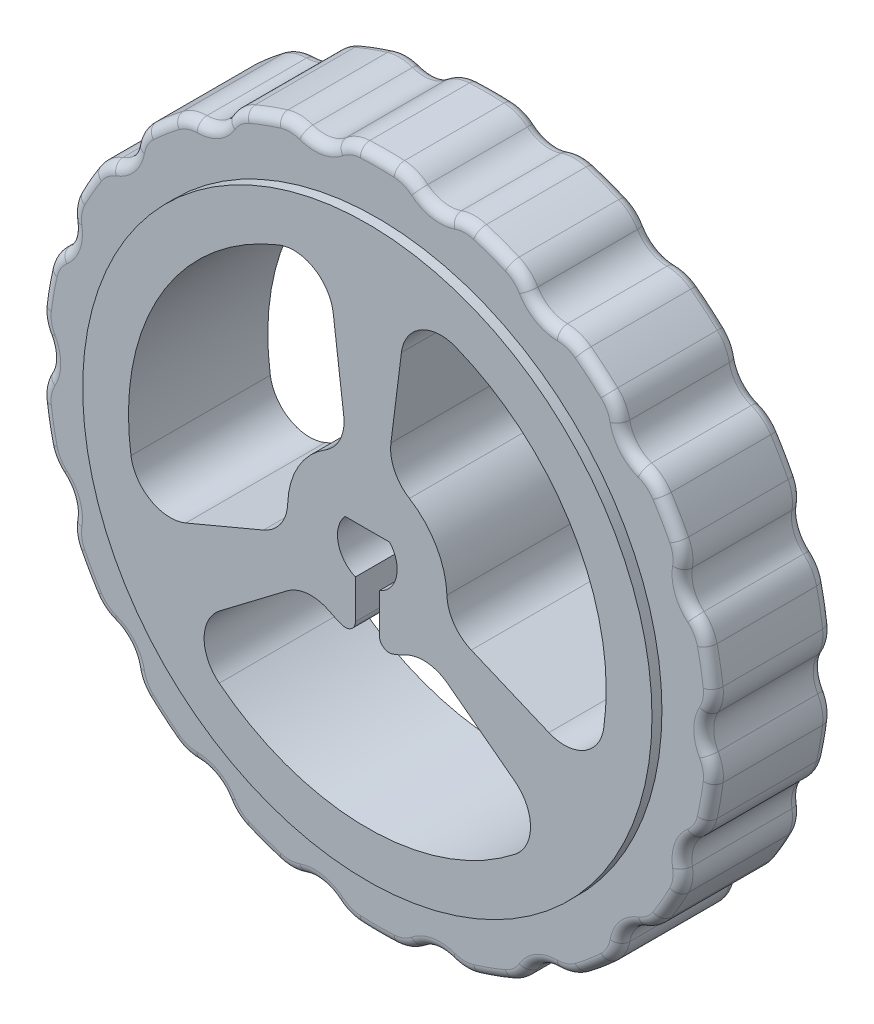
SolidWorks part; units mm, degrees
material "ABS"
ref_plane "前视基准面" through (0, 0, 0) normal (0, 0, 1) x (1, 0, 0)
ref_plane "上视基准面" through (0, 0, 0) normal (0, 1, 0) x (1, 0, 0)
ref_plane "右视基准面" through (0, 0, 0) normal (1, 0, 0) x (0, 0, -1)
sketch "草图1" plane through (0, 0, 0) normal (0, 0, 1) x (1, 0, 0)
  line L0 (0, 0) -> (0, 20.2054) construction
  line L1 (-2, 11.8322) -> (-1, 3.873)
  line L2 (2, 11.8322) -> (1, 3.873)
  line L3 (11.247, -4.184) -> (3.8541, -1.0705)
  line L4 (9.247, -7.6481) -> (2.8541, -2.8025)
  line L5 (-9.247, -7.6481) -> (-2.8541, -2.8025)
  line L6 (-11.247, -4.184) -> (-3.8541, -1.0705)
  line L7 (1.118, 1) -> (-1.118, 1)
  line L8 (0.6, -3.9547) -> (0.6, -1.3748)
  line L9 (-0.6, -3.9547) -> (-0.6, -1.3748)
  circle A0 centre (0, 0) radius 17
  arc A1 (-2, 11.8322) -> (-11.247, -4.184) centre (0, 0) ccw
  arc A2 (-1.118, 1) -> (-0.6, -1.3748) centre (0, 0) ccw
  arc A3 (-1, 3.873) -> (-3.8541, -1.0705) centre (0, 0) ccw
  arc A4 (-9.247, -7.6481) -> (9.247, -7.6481) centre (0, 0) ccw
  arc A5 (-2.8541, -2.8025) -> (-0.6, -3.9547) centre (0, 0) ccw
  arc A6 (3.8541, -1.0705) -> (1, 3.873) centre (0, 0) ccw
  arc A7 (11.247, -4.184) -> (2, 11.8322) centre (0, 0) ccw
  arc A8 (0.6, -1.3748) -> (1.118, 1) centre (0, 0) ccw
  arc A9 (0.6, -3.9547) -> (2.8541, -2.8025) centre (0, 0) ccw
  point P19 (0, 0)
  dimension "D1" = 34
  dimension "D2" = 3
  dimension "D3" = 4
  dimension "D4" = 12
  dimension "D5" = 1
  dimension "D6" = 2
  dimension "D8" = 1
  dimension "D9" = 1.2
  dimension "D7" = 3
extrude "凸台-拉伸1" add sketch "草图1" along normal mid plane 6
sketch "草图3" plane through (0, 0, 0) normal (0, 0, 1) x (1, 0, 0)
  line L2 (2, 11.8322) -> (1, 3.873)
  line L3 (3.8541, -1.0705) -> (11.247, -4.184)
  line L4 (2, 11.8322) -> (1, 3.873)
  line L5 (3.8541, -1.0705) -> (11.247, -4.184)
  line L6 (-1, 3.873) -> (-2, 11.8322)
  line L7 (-11.247, -4.184) -> (-3.8541, -1.0705)
  line L8 (-1, 3.873) -> (-2, 11.8322)
  line L9 (-11.247, -4.184) -> (-3.8541, -1.0705)
  line L10 (-2.8541, -2.8025) -> (-9.247, -7.6481)
  line L11 (9.247, -7.6481) -> (2.8541, -2.8025)
  line L12 (-2.8541, -2.8025) -> (-9.247, -7.6481)
  line L13 (9.247, -7.6481) -> (2.8541, -2.8025)
  line L17 (1.118, 1) -> (-1.118, 1)
  line L18 (1.118, 1) -> (-1.118, 1)
  line L19 (0.6, -3.9547) -> (0.6, -1.3748)
  line L20 (0.6, -3.9547) -> (0.6, -1.3748)
  line L21 (9.247, -7.6481) -> (2.8541, -2.8025)
  line L23 (-2.8541, -2.8025) -> (-9.247, -7.6481)
  line L24 (-2.8541, -2.8025) -> (-9.247, -7.6481)
  line L25 (-0.6, -1.3748) -> (-0.6, -3.9547)
  line L26 (-0.6, -1.3748) -> (-0.6, -3.9547)
  line L27 (-0.6, -1.3748) -> (-0.6, -3.9547)
  line L28 (-0.6, -1.3748) -> (-0.6, -3.9547)
  line L29 (1.118, 1) -> (-1.118, 1)
  line L30 (1.118, 1) -> (-1.118, 1)
  line L31 (0.6, -3.9547) -> (0.6, -1.3748)
  line L32 (0.6, -3.9547) -> (0.6, -1.3748)
  circle A0 centre (0, 0) radius 14.3
  arc A1 (3.8541, -1.0705) -> (1, 3.873) centre (0, 0) ccw
  arc A2 (-1.118, 1) -> (-0.6, -1.3748) centre (0, 0) ccw
  arc A3 (-1.118, 1) -> (-0.6, -1.3748) centre (0, 0) ccw
  arc A4 (-2.8541, -2.8025) -> (2.8541, -2.8025) centre (0, 0) ccw
  arc A6 (-1, 3.873) -> (-3.8541, -1.0705) centre (0, 0) ccw
  arc A7 (3.8541, -1.0705) -> (1, 3.873) centre (0, 0) ccw
  arc A8 (11.247, -4.184) -> (2, 11.8322) centre (0, 0) ccw
  arc A9 (3.8541, -1.0705) -> (1, 3.873) centre (0, 0) ccw
  arc A10 (11.247, -4.184) -> (2, 11.8322) centre (0, 0) ccw
  arc A11 (-1, 3.873) -> (-3.8541, -1.0705) centre (0, 0) ccw
  arc A12 (-2, 11.8322) -> (-11.247, -4.184) centre (0, 0) ccw
  arc A13 (-1, 3.873) -> (-3.8541, -1.0705) centre (0, 0) ccw
  arc A14 (-2, 11.8322) -> (-11.247, -4.184) centre (0, 0) ccw
  arc A15 (-2.8541, -2.8025) -> (-0.6, -3.9547) centre (0, 0) ccw
  arc A16 (-9.247, -7.6481) -> (9.247, -7.6481) centre (0, 0) ccw
  arc A17 (-2.8541, -2.8025) -> (-0.6, -3.9547) centre (0, 0) ccw
  arc A18 (-9.247, -7.6481) -> (9.247, -7.6481) centre (0, 0) ccw
  arc A21 (0.6, -1.3748) -> (1.118, 1) centre (0, 0) ccw
  arc A22 (0.6, -1.3748) -> (1.118, 1) centre (0, 0) ccw
  arc A23 (0.6, -3.9547) -> (2.8541, -2.8025) centre (0, 0) ccw
  arc A24 (0.6, -3.9547) -> (2.8541, -2.8025) centre (0, 0) ccw
  arc A25 (-9.247, -7.6481) -> (9.247, -7.6481) centre (0, 0) ccw
  arc A26 (-9.247, -7.6481) -> (9.247, -7.6481) centre (0, 0) ccw
  arc A27 (-2.8541, -2.8025) -> (-0.6, -3.9547) centre (0, 0) ccw
  arc A28 (-2.8541, -2.8025) -> (-0.6, -3.9547) centre (0, 0) ccw
  arc A29 (-1.118, 1) -> (-0.6, -1.3748) centre (0, 0) ccw
  arc A30 (-1.118, 1) -> (-0.6, -1.3748) centre (0, 0) ccw
  arc A31 (0.6, -1.3748) -> (1.118, 1) centre (0, 0) ccw
  arc A32 (0.6, -1.3748) -> (1.118, 1) centre (0, 0) ccw
  arc A33 (0.6, -3.9547) -> (2.8541, -2.8025) centre (0, 0) ccw
  arc A34 (0.6, -3.9547) -> (2.8541, -2.8025) centre (0, 0) ccw
  dimension "D1" = 28.6
  dimension "D2" = 0
  dimension "D4" = 0
  dimension "D5" = 0
  dimension "D6" = 0
extrude "凸台-拉伸2" add sketch "草图3" along normal mid plane 7 contours A0 A22 L20 A4 L13 A18 L12 L26 A3 L18 A14 L8 A6 L9 A10 L5 A1 L4 region at (-13.8955, 0, 0)
sketch "草图4" plane through (0, 0, 3) normal (0, 0, 1) x (1, 0, 0)
  line L0 (0, 0) -> (-21.4662, 0) construction
  line L1 (-16.4, 0) -> (-16.4, -8.2545) construction
  line L2 (-17, 0) -> (-17, -7.6695) construction
  line L3 (0, 0) -> (-16.1508, 2.8478) construction
  line L4 (-16.1508, 2.8478) -> (-16.7417, 2.952)
  line L5 (0, 0) -> (-17.0419, 6.2027) construction
  arc A0 (-16.4, 0) -> (-17.1432, 1.4239) centre (-18.1356, 0) ccw
  circle A1 centre (0, 0) radius 17 construction
  arc A2 (-16.5964, 4.5253) -> (-17.1432, 1.4239) centre (-16.1508, 2.8478) ccw
  circle A3 centre (0, 0) radius 18.1356 construction
  arc A4 (-16.5964, 4.5253) -> (-15.411, 5.6091) centre (-17.0419, 6.2027) ccw
  arc A5 (-14.0478, 9.9287) -> (-12.5631, 10.5417) centre (-13.8927, 11.6573) ccw
  arc A6 (-14.0478, 9.9287) -> (-15.6224, 7.2014) centre (-14.2028, 8.2) ccw
  arc A7 (-15.411, 5.6091) -> (-15.6224, 7.2014) centre (-17.0419, 6.2027) ccw
  arc A8 (-9.8048, 14.1345) -> (-8.2, 14.2028) centre (-9.0678, 15.7059) ccw
  arc A9 (-9.8048, 14.1345) -> (-12.2172, 12.1102) centre (-10.5417, 12.5631) ccw
  arc A10 (-12.5631, 10.5417) -> (-12.2172, 12.1102) centre (-13.8927, 11.6573) ccw
  arc A11 (-4.3792, 16.6355) -> (-2.8478, 16.1508) centre (-3.1492, 17.8601) ccw
  arc A12 (-4.3792, 16.6355) -> (-7.3385, 15.5584) centre (-5.6091, 15.411) ccw
  arc A13 (-8.2, 14.2028) -> (-7.3385, 15.5584) centre (-9.0678, 15.7059) ccw
  arc A14 (1.5746, 17.13) -> (2.8478, 16.1508) centre (3.1492, 17.8601) ccw
  arc A15 (1.5746, 17.13) -> (-1.5746, 17.13) centre (0, 16.4) ccw
  arc A16 (-2.8478, 16.1508) -> (-1.5746, 17.13) centre (-3.1492, 17.8601) ccw
  arc A17 (7.3385, 15.5584) -> (8.2, 14.2028) centre (9.0678, 15.7059) ccw
  arc A18 (7.3385, 15.5584) -> (4.3792, 16.6355) centre (5.6091, 15.411) ccw
  arc A19 (2.8478, 16.1508) -> (4.3792, 16.6355) centre (3.1492, 17.8601) ccw
  arc A20 (12.2172, 12.1102) -> (12.5631, 10.5417) centre (13.8927, 11.6573) ccw
  arc A21 (12.2172, 12.1102) -> (9.8048, 14.1345) centre (10.5417, 12.5631) ccw
  arc A22 (8.2, 14.2028) -> (9.8048, 14.1345) centre (9.0678, 15.7059) ccw
  arc A23 (15.6224, 7.2014) -> (15.411, 5.6091) centre (17.0419, 6.2027) ccw
  arc A24 (15.6224, 7.2014) -> (14.0478, 9.9287) centre (14.2028, 8.2) ccw
  arc A25 (12.5631, 10.5417) -> (14.0478, 9.9287) centre (13.8927, 11.6573) ccw
  arc A26 (17.1432, 1.4239) -> (16.4, 0) centre (18.1356, 0) ccw
  arc A27 (17.1432, 1.4239) -> (16.5964, 4.5253) centre (16.1508, 2.8478) ccw
  arc A28 (15.411, 5.6091) -> (16.5964, 4.5253) centre (17.0419, 6.2027) ccw
  arc A29 (16.5964, -4.5253) -> (15.411, -5.6091) centre (17.0419, -6.2027) ccw
  arc A30 (16.5964, -4.5253) -> (17.1432, -1.4239) centre (16.1508, -2.8478) ccw
  arc A31 (16.4, 0) -> (17.1432, -1.4239) centre (18.1356, 0) ccw
  arc A32 (14.0478, -9.9287) -> (12.5631, -10.5417) centre (13.8927, -11.6573) ccw
  arc A33 (14.0478, -9.9287) -> (15.6224, -7.2014) centre (14.2028, -8.2) ccw
  arc A34 (15.411, -5.6091) -> (15.6224, -7.2014) centre (17.0419, -6.2027) ccw
  arc A35 (9.8048, -14.1345) -> (8.2, -14.2028) centre (9.0678, -15.7059) ccw
  arc A36 (9.8048, -14.1345) -> (12.2172, -12.1102) centre (10.5417, -12.5631) ccw
  arc A37 (12.5631, -10.5417) -> (12.2172, -12.1102) centre (13.8927, -11.6573) ccw
  arc A38 (4.3792, -16.6355) -> (2.8478, -16.1508) centre (3.1492, -17.8601) ccw
  arc A39 (4.3792, -16.6355) -> (7.3385, -15.5584) centre (5.6091, -15.411) ccw
  arc A40 (8.2, -14.2028) -> (7.3385, -15.5584) centre (9.0678, -15.7059) ccw
  arc A41 (-1.5746, -17.13) -> (-2.8478, -16.1508) centre (-3.1492, -17.8601) ccw
  arc A42 (-1.5746, -17.13) -> (1.5746, -17.13) centre (0, -16.4) ccw
  arc A43 (2.8478, -16.1508) -> (1.5746, -17.13) centre (3.1492, -17.8601) ccw
  arc A44 (-7.3385, -15.5584) -> (-8.2, -14.2028) centre (-9.0678, -15.7059) ccw
  arc A45 (-7.3385, -15.5584) -> (-4.3792, -16.6355) centre (-5.6091, -15.411) ccw
  arc A46 (-2.8478, -16.1508) -> (-4.3792, -16.6355) centre (-3.1492, -17.8601) ccw
  arc A47 (-12.2172, -12.1102) -> (-12.5631, -10.5417) centre (-13.8927, -11.6573) ccw
  arc A48 (-12.2172, -12.1102) -> (-9.8048, -14.1345) centre (-10.5417, -12.5631) ccw
  arc A49 (-8.2, -14.2028) -> (-9.8048, -14.1345) centre (-9.0678, -15.7059) ccw
  arc A50 (-15.6224, -7.2014) -> (-15.411, -5.6091) centre (-17.0419, -6.2027) ccw
  arc A51 (-15.6224, -7.2014) -> (-14.0478, -9.9287) centre (-14.2028, -8.2) ccw
  arc A52 (-12.5631, -10.5417) -> (-14.0478, -9.9287) centre (-13.8927, -11.6573) ccw
  arc A53 (-17.1432, -1.4239) -> (-16.4, 0) centre (-18.1356, 0) ccw
  arc A54 (-17.1432, -1.4239) -> (-16.5964, -4.5253) centre (-16.1508, -2.8478) ccw
  arc A55 (-15.411, -5.6091) -> (-16.5964, -4.5253) centre (-17.0419, -6.2027) ccw
  circle A56 centre (0, 0) radius 23.1579
  point P139 (0, 0)
  dimension "D1" = 0.6
  dimension "D2" = 20
  dimension "D3" = 0.6
  dimension "D4" = 18
extrude "切除-拉伸2" cut sketch "草图4" against normal blind 7 contours A56 A1 A55 A54 A53 A0 A2 A4 A7 A6 A5 A10 A9 A8 A13 A12 A11 A16 A15 A14 A19 A18 A17 A22 A21 A20 A25 A24 A23 A28 A27 A26 A31 A30 A29 A34 A33 A32 | A5 A10 A1 | A8 A13 A1 | A11 A16 A1 | A14 A19 A1 | A17 A22 A1 | A20 A25 A1 | A23 A28 A1 | A26 A31 A1 | A29 A34 A1 | A32 A37 A1 | A35 A40 A1 | A38 A43 A1 | A41 A46 A1 | A44 A49 A1 | A47 A52 A1 | A1 A53 A0 | A50 A55 A1 | A4 A7 A1 region at (-16.7468, 0, 3) region at (-15.7369, -5.7277, 3) region at (-15.7369, 5.7277, 3) region at (-12.8288, -10.7646, 3) region at (-12.8288, 10.7646, 3) region at (-8.3734, -14.5032, 3) region at (-8.3734, 14.5032, 3) region at (-2.9081, -16.4924, 3) region at (-2.9081, 16.4924, 3) region at (2.9081, -16.4924, 3) region at (2.9081, 16.4924, 3) region at (8.3734, -14.5032, 3) region at (8.3734, 14.5032, 3) region at (12.8288, -10.7646, 3) region at (12.8288, 10.7646, 3) region at (15.7369, -5.7277, 3) region at (15.7369, 5.7277, 3) region at (16.7468, 0, 3) region at (-22.5029, 0, 3)
fillet "圆角1" radius 2 36 edges at (-13.8026, 9.9241, 0) (-12.1701, 11.8696, 0) (-9.576, 14.0464, 0) (-7.3765, 15.3162, 0) (-4.1944, 16.4744, 0) (-1.6932, 16.9155, 0) (1.6932, 16.9155, 0) (4.1944, 16.4744, 0) (7.3765, 15.3162, 0) (9.576, 14.0464, 0) (12.1701, 11.8696, 0) (13.8026, 9.9241, 0) (15.4958, 6.9914, 0) (16.3645, 4.6048, 0) (16.9525, 1.2699, 0) (16.9525, -1.2699, 0) (16.3645, -4.6048, 0) (15.4958, -6.9914, 0) (13.8026, -9.9241, 0) (12.1701, -11.8696, 0) (9.576, -14.0464, 0) (7.3765, -15.3162, 0) (4.1944, -16.4744, 0) (1.6932, -16.9155, 0) (-1.6932, -16.9155, 0) (-4.1944, -16.4744, 0) (-7.3765, -15.3162, 0) (-9.576, -14.0464, 0) (-12.1701, -11.8696, 0) (-15.4958, -6.9914, 0) (-13.8026, -9.9241, 0) (-16.3645, -4.6048, 0) (-16.9525, -1.2699, 0) (-16.9525, 1.2699, 0) (-16.3645, 4.6048, 0) (-15.4958, 6.9914, 0)
fillet "圆角2" radius 0.5 144 edges at (-16.8479, -1.4528, 3) (-16.7417, -2.952, 3) (-16.3287, -4.3971, 3) (-15.411, -5.6091, 3) (-15.3349, -7.1275, 3) (-14.7224, -8.5, 3) (-13.8401, -9.7167, 3) (-12.5631, -10.5417, 3) (-11.9724, -11.9425, 3) (-10.9274, -13.0228, 3) (-9.6821, -13.8643, 3) (-8.2, -14.2028, 3) (-7.1658, -15.3171, 3) (-5.8143, -15.9748, 3) (-4.3564, -16.3397, 3) (-2.8478, -16.1508, 3) (-1.4949, -16.8442, 3) (0, -17, 3) (1.4949, -16.8442, 3) (2.8478, -16.1508, 3) (4.3564, -16.3397, 3) (5.8143, -15.9748, 3) (7.1658, -15.3171, 3) (8.2, -14.2028, 3) (9.6821, -13.8643, 3) (10.9274, -13.0228, 3) (11.9724, -11.9425, 3) (12.5631, -10.5417, 3) (13.8401, -9.7167, 3) (14.7224, -8.5, 3) (15.3349, -7.1275, 3) (15.411, -5.6091, 3) (16.3287, -4.3971, 3) (16.7417, -2.952, 3) (16.8479, -1.4528, 3) (16.4, 0, 3) (16.8479, 1.4528, 3) (16.7417, 2.952, 3) (16.3287, 4.3971, 3) (15.411, 5.6091, 3) (15.3349, 7.1275, 3) (14.7224, 8.5, 3) (13.8401, 9.7167, 3) (12.5631, 10.5417, 3) (11.9724, 11.9425, 3) (10.9274, 13.0228, 3) (9.6821, 13.8643, 3) (8.2, 14.2028, 3) (7.1658, 15.3171, 3) (5.8143, 15.9748, 3) (4.3564, 16.3397, 3) (2.8478, 16.1508, 3) (1.4949, 16.8442, 3) (0, 17, 3) (-1.4949, 16.8442, 3) (-2.8478, 16.1508, 3) (-4.3564, 16.3397, 3) (-5.8143, 15.9748, 3) (-7.1658, 15.3171, 3) (-8.2, 14.2028, 3) (-9.6821, 13.8643, 3) (-10.9274, 13.0228, 3) (-11.9724, 11.9425, 3) (-12.5631, 10.5417, 3) (-13.8401, 9.7167, 3) (-14.7224, 8.5, 3) (-15.3349, 7.1275, 3) (-15.411, 5.6091, 3) (-16.3287, 4.3971, 3) (-16.7417, 2.952, 3) (-16.8479, 1.4528, 3) (-16.4, 0, 3) (-16.8479, -1.4528, -3) (-16.7417, -2.952, -3) (-16.3287, -4.3971, -3) (-15.411, -5.6091, -3) (-15.3349, -7.1275, -3) (-14.7224, -8.5, -3) (-13.8401, -9.7167, -3) (-12.5631, -10.5417, -3) (-11.9724, -11.9425, -3) (-10.9274, -13.0228, -3) (-9.6821, -13.8643, -3) (-8.2, -14.2028, -3) (-7.1658, -15.3171, -3) (-5.8143, -15.9748, -3) (-4.3564, -16.3397, -3) (-2.8478, -16.1508, -3) (-1.4949, -16.8442, -3) (0, -17, -3) (1.4949, -16.8442, -3) (2.8478, -16.1508, -3) (4.3564, -16.3397, -3) (5.8143, -15.9748, -3) (7.1658, -15.3171, -3) (8.2, -14.2028, -3) (9.6821, -13.8643, -3) (10.9274, -13.0228, -3) (11.9724, -11.9425, -3) (12.5631, -10.5417, -3) (13.8401, -9.7167, -3) (14.7224, -8.5, -3) (15.3349, -7.1275, -3) (15.411, -5.6091, -3) (16.3287, -4.3971, -3) (16.7417, -2.952, -3) (16.8479, -1.4528, -3) (16.4, 0, -3) (16.8479, 1.4528, -3) (16.7417, 2.952, -3) (16.3287, 4.3971, -3) (15.411, 5.6091, -3) (15.3349, 7.1275, -3) (14.7224, 8.5, -3) (13.8401, 9.7167, -3) (12.5631, 10.5417, -3) (11.9724, 11.9425, -3) (10.9274, 13.0228, -3) (9.6821, 13.8643, -3) (8.2, 14.2028, -3) (7.1658, 15.3171, -3) (5.8143, 15.9748, -3) (4.3564, 16.3397, -3) (2.8478, 16.1508, -3) (1.4949, 16.8442, -3) (0, 17, -3) (-1.4949, 16.8442, -3) (-2.8478, 16.1508, -3) (-4.3564, 16.3397, -3) (-5.8143, 15.9748, -3) (-7.1658, 15.3171, -3) (-8.2, 14.2028, -3) (-9.6821, 13.8643, -3) (-10.9274, 13.0228, -3) (-11.9724, 11.9425, -3) (-12.5631, 10.5417, -3) (-13.8401, 9.7167, -3) (-14.7224, 8.5, -3) (-15.3349, 7.1275, -3) (-15.411, 5.6091, -3) (-16.3287, 4.3971, -3) (-16.7417, 2.952, -3) (-16.8479, 1.4528, -3) (-16.4, 0, -3)
fillet "圆角3" radius 2 6 edges at (2.8541, -2.8025, 0) (-2.8541, -2.8025, 0) (-3.8541, -1.0705, 0) (-1, 3.873, 0) (1, 3.873, 0) (3.8541, -1.0705, 0)
fillet "圆角4" radius 0.5 2 edges at (-0.6, -3.9547, 0) (0.6, -3.9547, 0)
fillet "圆角5" radius 2 6 edges at (-9.247, -7.6481, 0) (-11.247, -4.184, 0) (-2, 11.8322, 0) (2, 11.8322, 0) (11.247, -4.184, 0) (9.247, -7.6481, 0)
